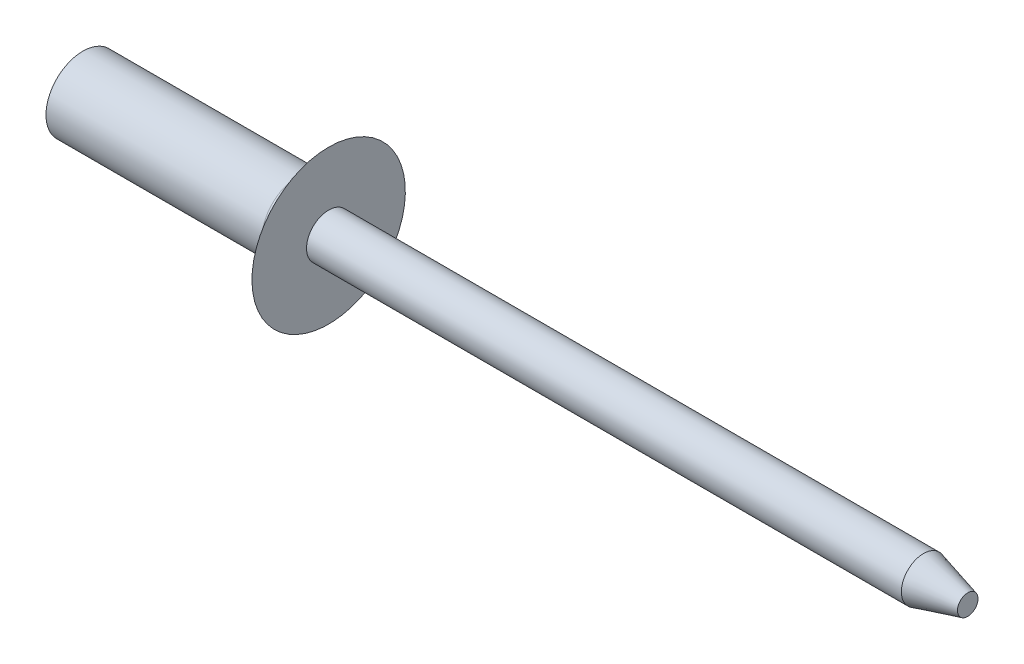
SolidWorks part; units mm, degrees
ref_plane "Front" through (0, 0, 0) normal (0, 0, 1) x (1, 0, 0)
ref_plane "Top" through (0, 0, 0) normal (0, 1, 0) x (1, 0, 0)
ref_plane "Right" through (0, 0, 0) normal (1, 0, 0) x (0, 0, -1)
sketch "Sketch1" plane through (-20.7953, 23.9153, 0) normal (0, 0, 1) x (0, -1, 0)
  line L0 (23.9153, 20.7953) -> (25.4153, 20.7953)
  line L1 (25.4153, 20.7953) -> (25.4153, 29.86)
  line L2 (25.4153, 29.86) -> (27.0353, 30.7953)
  line L3 (27.0353, 30.7953) -> (24.8153, 30.7953)
  line L4 (24.8153, 30.7953) -> (24.8153, 56.7953)
  line L5 (23.9153, 51.1695) -> (23.9153, -6.4589) construction
  line L6 (24.8153, 56.7953) -> (23.9153, 56.7953)
  line L7 (23.9153, 56.7953) -> (23.9153, 20.7953)
  dimension "D5" = 60
revolve "Base-Revolve" add sketch "Sketch1" angle 360 about L5
fillet "Fillet1" radius 0.5 1 edges at (9.0647, 1.5, 0)
chamfer "Chamfer1" distance 1.8 angle 15 1 edges at (36, 0.9, 0) first distance on face at (36, 0.9, 0)
equation "\"D1@Chamfer1\" = \"d1@Sketch1\""
